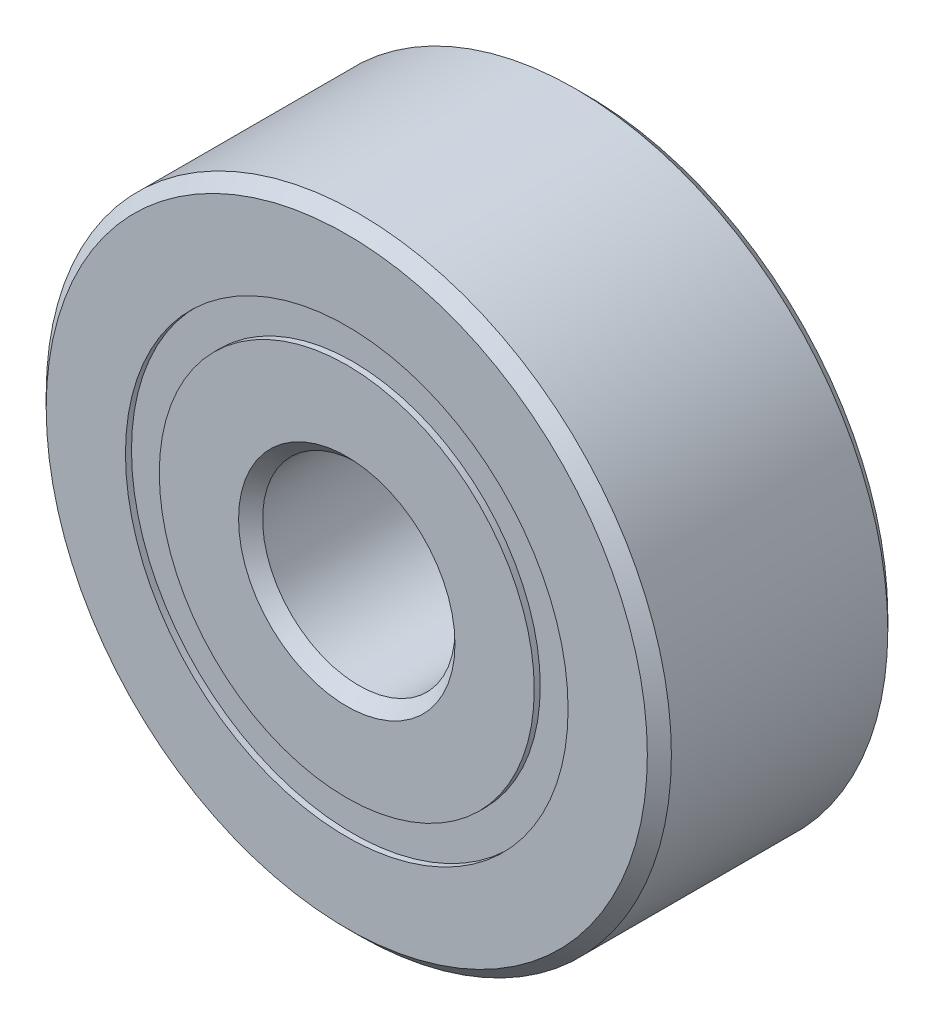
SolidWorks part; units mm, degrees
ref_plane "Front Plane" through (0, 0, 0) normal (0, 0, 1) x (1, 0, 0)
ref_plane "Top Plane" through (0, 0, 0) normal (0, 1, 0) x (1, 0, 0)
ref_plane "Right Plane" through (0, 0, 0) normal (1, 0, 0) x (0, 0, -1)
sketch "Sketch1" plane through (0, 0, 0) normal (1, 0, 0) x (0, 0, -1)
  line L0 (-2.5, 0) -> (2.5, 0) construction
  line L1 (0, 6.5) -> (0, -6.5) construction
  line L2 (2.25, 6.5) -> (-2.25, 6.5)
  line L3 (-2.25, 6.5) -> (-2.5, 6.25)
  line L4 (-2.5, 6.25) -> (-2.5, 4.6016)
  line L5 (-2.5, 4.6016) -> (-1.1111, 4.6016)
  line L6 (2.5, 4.6016) -> (1.1111, 4.6016)
  line L7 (2.5, 6.25) -> (2.5, 4.6016)
  line L8 (2.25, 6.5) -> (2.5, 6.25)
  line L9 (0, 6.5) -> (0, 4.25) construction
  line L10 (0, 4.25) -> (0, 2) construction
  arc A0 (-1.1111, 4.6016) -> (1.1111, 4.6016) centre (0, 4.25) cw
  point P14 (0, 2)
  dimension "D3" = 2.2222
  dimension "D1" = 45
  dimension "Width" = 5
  dimension "OD" = 13
  dimension "D2" = 0.25
  dimension "Shaft Dia" = 4
  dimension "D4" = 0.3516
revolve "Revolve1" add sketch "Sketch1" angle 360 about L0
sketch "Sketch3" plane through (0, 0, 0) normal (1, 0, 0) x (0, 0, -1)
  line L0 (-2.5, 3.8984) -> (-1.1111, 3.8984)
  line L1 (0, 6.5) -> (0, -6.5) construction
  line L2 (-2.5, 6.25) -> (-2.5, 4.6016) construction
  line L3 (-2.5, 3.8984) -> (-2.5, 2.25)
  line L4 (-2.25, 6.5) -> (-2.5, 6.25) construction
  line L5 (-2.5, 2.25) -> (-2.25, 2)
  line L6 (-2.25, 2) -> (2.25, 2)
  line L7 (2.25, 6.5) -> (2.25, -6.5) construction
  line L8 (2.25, 2) -> (2.5, 2.25)
  line L9 (2.5, -6.25) -> (2.5, 6.25) construction
  line L10 (2.5, 2.25) -> (2.5, 3.8984)
  line L11 (2.5, 3.8984) -> (1.1111, 3.8984)
  line L13 (2.25, 6.5) -> (2.5, 6.25) construction
  arc A0 (1.1111, 4.6016) -> (-1.1111, 4.6016) centre (0, 4.25) ccw construction
  arc A1 (1.1111, 3.8984) -> (-1.1111, 3.8984) centre (0, 4.25) cw
revolve "Revolve3" add sketch "Sketch3" angle 360 about L0
sketch "Sketch4" plane through (0, 0, 0) normal (1, 0, 0) x (0, 0, -1)
  line L0 (-1.1654, 4.25) -> (1.1654, 4.25)
  arc A2 (-1.1654, 4.25) -> (1.1654, 4.25) centre (0, 4.25) cw
  arc A3 (1.1111, 4.6016) -> (-1.1111, 4.6016) centre (0, 4.25) ccw construction
revolve "Revolve4" add sketch "Sketch4" angle 360 about L0
ref_axis "Axis1" through (0, 0, -2.5) along (0, 0, 1)
pattern_circular "CirPattern1" count 12 every 30 about axis through (0, 0, -2.5) along (0, 0, 1) of bodies 104
sketch "Sketch5" plane through (0, 0, 0) normal (1, 0, 0) x (0, 0, -1)
  line L0 (-2.5, 4.6016) -> (-1.1111, 4.6016) construction
  line L1 (-2.375, 4.6016) -> (-1.1654, 4.6016)
  line L2 (-2.375, 4.6016) -> (-2.375, 3.8984)
  line L3 (-2.375, 3.8984) -> (-1.1654, 3.8984)
  line L4 (-1.1654, 4.6016) -> (-1.1654, 3.8984)
  line L5 (-2.5, 3.8984) -> (-1.1111, 3.8984) construction
  line L6 (2.5, 4.6016) -> (1.1111, 4.6016) construction
  line L7 (2.375, 4.6016) -> (1.1654, 4.6016)
  line L8 (2.375, 4.6016) -> (2.375, 3.8984)
  line L9 (2.375, 3.8984) -> (1.1654, 3.8984)
  line L10 (1.1654, 4.6016) -> (1.1654, 3.8984)
  line L11 (2.5, 3.8984) -> (1.1111, 3.8984) construction
  line L12 (-2.25, 6.5) -> (-2.5, 6.25) construction
  point P18 (-2.375, 6.375)
revolve "Revolve5" add sketch "Sketch5" angle 360 about L0
sketch "Sketch6" plane through (0, 0, 0) normal (1, 0, 0) x (0, 0, -1)
  line L0 (2.5, 0) -> (-2.5, 0) construction
  line L1 (2.5, 4.6016) -> (1.4, 4.6016)
  line L2 (2.5, 4.6016) -> (2.5, 9.5)
  line L3 (2.5, 9.5) -> (1.4, 9.5)
  line L4 (1.4, 4.6016) -> (1.4, 9.5)
  dimension "Th" = 1.1
  dimension "Flange OD" = 19
revolve "Revolve6" [suppressed] add sketch "Sketch6" angle 360 about L0
equation "\"D2@Sketch1\" = \"Width@Sketch1\"*.05"
equation "\"D3@Sketch1\" = \"Width@Sketch1\"/2.25"
equation "\"D4@Sketch1\" = (((\"OD@Sketch1\"-\"Width@Sketch1\")/2)/3.25)/3.5"
equation "\"D2@CirPattern1\" = 360/\"Balls@CirPattern1\""
